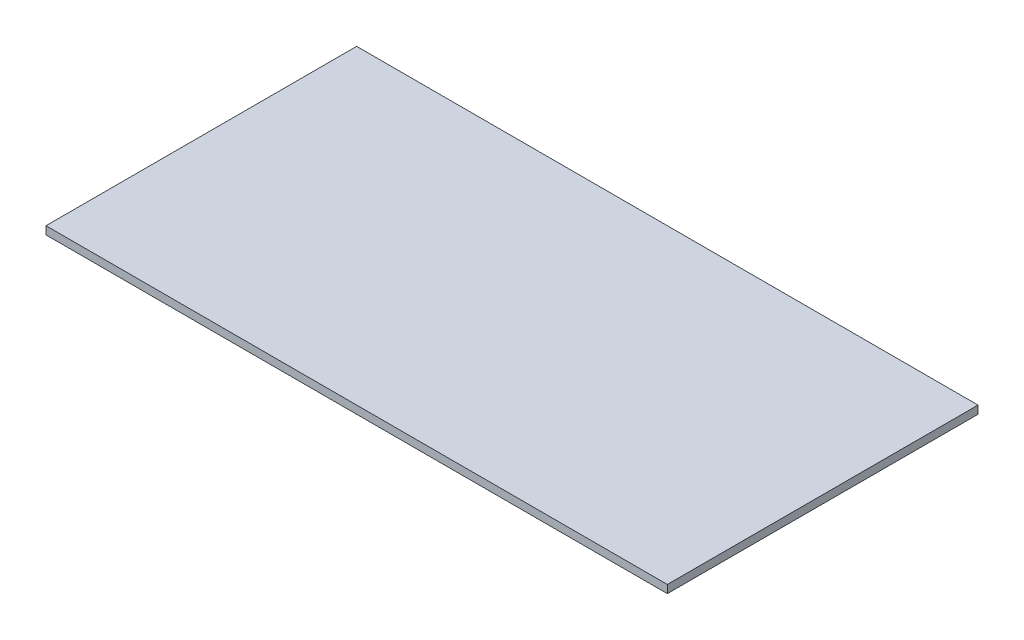
SolidWorks part; units mm, degrees
material "Cedar"
ref_plane "Front Plane" through (0, 0, 0) normal (0, 0, 1) x (1, 0, 0)
ref_plane "Top Plane" through (0, 0, 0) normal (0, 1, 0) x (1, 0, 0)
ref_plane "Right Plane" through (0, 0, 0) normal (1, 0, 0) x (0, 0, -1)
sketch "Sketch1" plane through (0, 0, 0) normal (0, 1, 0) x (1, 0, 0)
  line L1 (700, -350) -> (-700, -350)
  line L2 (700, -350) -> (700, 350)
  line L3 (700, 350) -> (-700, 350)
  line L4 (-700, -350) -> (-700, 350)
  line L5 (700, -350) -> (-700, 350) construction
  line L6 (700, 350) -> (-700, -350) construction
  point P0 (0, 0)
  dimension "D1" = 700
  dimension "D2" = 1400
extrude "Boss-Extrude1" add sketch "Sketch1" along normal blind 18
